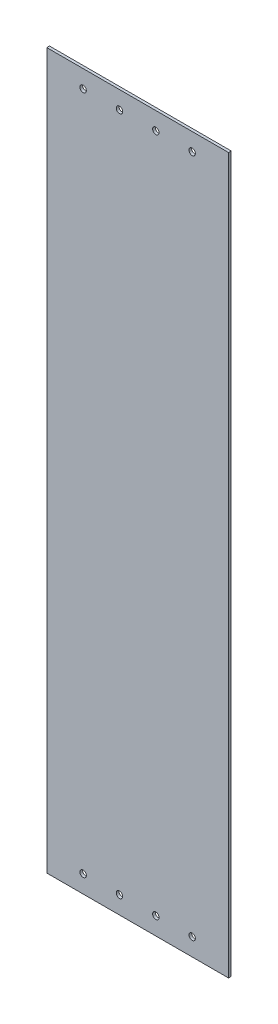
SolidWorks part; units mm, degrees
material "5052-H32"
ref_plane "Front Plane" through (0, 0, 0) normal (0, 0, 1) x (1, 0, 0)
ref_plane "Top Plane" through (0, 0, 0) normal (0, 1, 0) x (1, 0, 0)
ref_plane "Right Plane" through (0, 0, 0) normal (1, 0, 0) x (0, 0, -1)
sketch "Sketch1" plane through (0, 0, 0) normal (0, 0, 1) x (1, 0, 0)
  line L0 (55, 0) -> (-55, 0) construction
  line L1 (-77.5, 304.8) -> (77.5, 304.8)
  line L2 (-77.5, 304.8) -> (-77.5, -304.8)
  line L3 (-77.5, -304.8) -> (77.5, -304.8)
  line L4 (77.5, 304.8) -> (77.5, -304.8)
  line L5 (-77.5, 304.8) -> (77.5, -304.8) construction
  line L6 (-77.5, -304.8) -> (77.5, 304.8) construction
  point P0 (0, 0)
  point P20 (-46.5, 289.795)
  point P21 (-15.5, 289.795)
  point P23 (15.5, 289.795)
  point P24 (46.5, 289.795)
  point P33 (46.5, -289.795)
  point P34 (15.5, -289.795)
  point P35 (-15.5, -289.795)
  point P36 (-46.5, -289.795)
  dimension "D1" = 609.6
  dimension "D2" = 155
  dimension "D20" = 31
  dimension "D21" = 31
  dimension "D22" = 31
  dimension "D23" = 31
  dimension "D24" = 15.005
extrude "Boss-Extrude1" add sketch "Sketch1" along normal blind 2.305
hole_wizard "M5 Clearance Hole1" positions "Sketch2" profile "Sketch3" hole size "M5" standard "ANSI Metric" end condition through all
sketch "Sketch2" plane through (0, 0, 2.305) normal (0, 0, 1) x (1, 0, 0)
  point P0 (-46.5, 289.795)
  point P3 (-15.5, 289.795)
  point P6 (15.5, 289.795)
  point P9 (46.5, 289.795)
  point P12 (-46.5, -289.795)
  point P15 (-15.5, -289.795)
  point P18 (15.5, -289.795)
  point P21 (46.5, -289.795)
sketch "Sketch3" plane through (-46.5, 289.795, 2.305) normal (1, 0, 0) x (0, -1, 0)
  line L0 (0, 0) -> (0, 2.305)
  line L1 (0, 2.305) -> (2.75, 2.305)
  line L2 (2.75, 2.305) -> (2.75, 0)
  line L5 (2.75, 0) -> (0, 0)
  line L11 (0, -6.35) -> (0, 107.95) construction
  dimension "Thru Hole Dia." = 5.5
  dimension "Thru Hole Depth" = 2.305
